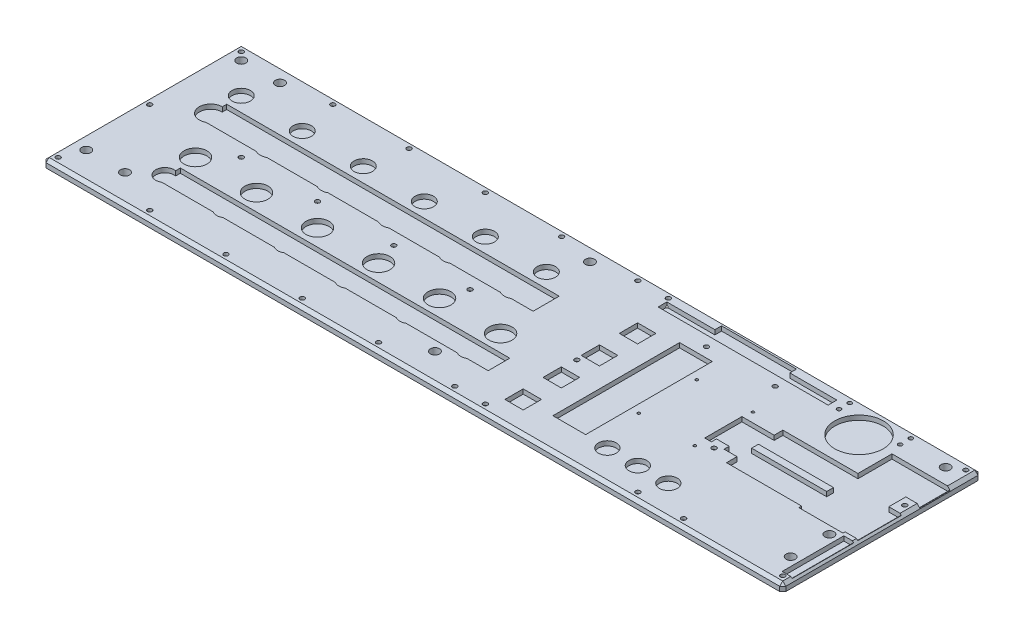
SolidWorks part; units mm, degrees
ref_plane "Front Plane" through (0, 0, 0) normal (0, 0, 1) x (1, 0, 0)
ref_plane "Top Plane" through (0, 0, 0) normal (0, 1, 0) x (1, 0, 0)
ref_plane "Right Plane" through (0, 0, 0) normal (1, 0, 0) x (0, 0, -1)
sketch "Sketch1" plane through (0, 0, 0) normal (0, 1, 0) x (1, 0, 0)
  line L1 (-180, 70) -> (305, 70)
  line L2 (-180, 70) -> (-180, -60)
  line L3 (-180, -60) -> (305, -60)
  line L4 (305, 70) -> (305, -60)
extrude "Boss-Extrude1" add sketch "Sketch1" against normal blind 5 from offset 1.6 offset against normal yes
sketch "Sketch2" plane through (0, -1.6, 0) normal (0, 1, 0) x (1, 0, 0)
  line L0 (305, 70) -> (-180, 70) construction
  line L1 (305, -60) -> (305, 70) construction
  line L2 (-180, 70) -> (-180, -60) construction
  circle A0 centre (245, 50.5) radius 15.0148 construction
  circle A1 centre (291.8, 60) radius 3
  circle A2 centre (-170, 60) radius 3
  circle A3 centre (-144.6, 60) radius 3
  circle A4 centre (58.6, 60) radius 3
  circle A5 centre (291.8, -16.2) radius 3
  circle A6 centre (291.8, -41.6) radius 3
  circle A7 centre (300, -55) radius 1.5
  circle A8 centre (-170, -41.6) radius 3
  circle A9 centre (-144.6, -41.6) radius 3
  circle A10 centre (58.6, -41.6) radius 3
  circle A11 centre (-175, 65) radius 1.5
  circle A12 centre (-115, 65) radius 1.5
  circle A13 centre (-65, 65) radius 1.5
  circle A14 centre (-15, 65) radius 1.5
  circle A15 centre (35, 65) radius 1.5
  circle A16 centre (85, 65) radius 1.5
  circle A17 centre (105, 65) radius 1.5
  circle A18 centre (300, 65) radius 1.5
  circle A19 centre (85, -55) radius 1.5
  circle A20 centre (105, -55) radius 1.5
  circle A21 centre (205, -55) radius 1.5
  circle A22 centre (235, -55) radius 1.5
  circle A23 centre (-175, -55) radius 1.5
  circle A24 centre (-115, -55) radius 1.5
  circle A25 centre (-65, -55) radius 1.5
  circle A26 centre (-15, -55) radius 1.5
  circle A27 centre (35, -55) radius 1.5
  circle A28 centre (-175, 5) radius 1.5
  circle A29 centre (-115, 5) radius 1.5
  circle A30 centre (-65, 5) radius 1.5
  circle A31 centre (110, 0) radius 1.5
  circle A32 centre (35, 5) radius 1.5
  circle A33 centre (-15, 5) radius 1.5
  circle A34 centre (205, -5) radius 1.5
  circle A35 centre (145, 50) radius 1.5
  circle A36 centre (190, 50) radius 1.5
  circle A37 centre (300, 25) radius 1.5
  circle A38 centre (160.54, 28.1) radius 0.879
  circle A39 centre (197.37, 28.1) radius 0.879
  circle A40 centre (197.37, -10) radius 0.879
  circle A41 centre (160.54, -10) radius 0.879
  dimension "D3" = 3
  dimension "D1" = 19.5
  dimension "D2" = 60
  dimension "D4" = 20
  dimension "D5" = 265
extrude "Cut-Extrude1" cut sketch "Sketch2" against normal through all
sketch "Sketch3" plane through (0, -1.6, 0) normal (0, 1, 0) x (1, 0, 0)
  line L0 (305, 70) -> (-180, 70) construction
  line L1 (305, -60) -> (305, 70) construction
  line L2 (208.9224, -2.3883) -> (217.3882, -2.3883)
  line L3 (266.5908, 50) -> (303.9819, 50)
  line L4 (266.5908, 50) -> (266.5908, 30.0739)
  line L5 (266.5908, 30.0739) -> (303.9819, 30.0739)
  line L6 (303.9819, 50) -> (303.9819, 30.0739)
  line L7 (288.3592, 18.9249) -> (303.1307, 18.9249)
  line L8 (288.3592, 18.9249) -> (288.3592, -9.6619)
  line L9 (288.3592, -9.6619) -> (303.1307, -9.6619)
  line L10 (303.1307, 18.9249) -> (303.1307, -9.6619)
  line L11 (297.3726, -12.3054) -> (303.1307, -12.3054)
  line L12 (297.3726, -12.3054) -> (297.3726, -52.7789)
  line L13 (297.3726, -52.7789) -> (303.1307, -52.7789)
  line L14 (303.1307, -12.3054) -> (303.1307, -52.7789)
  line L15 (217.3882, 27.6953) -> (268.8536, 27.6953)
  line L16 (217.3882, 27.6953) -> (217.3882, 21.977)
  line L17 (217.3882, 11.7004) -> (268.8536, 11.7004)
  line L18 (268.8536, 27.6953) -> (268.8536, 11.7004)
  line L19 (268.8536, 7.2252) -> (217.3882, 7.2252)
  line L20 (268.8536, 7.2252) -> (268.8536, -9.267)
  line L21 (268.8536, -9.267) -> (217.3882, -9.267)
  line L22 (217.3882, -2.3883) -> (217.3882, -9.267)
  line L23 (196.255, 21.977) -> (217.3882, 21.977)
  line L24 (196.255, 21.977) -> (196.255, -2.3883)
  line L25 (196.255, -2.3883) -> (200.5925, -2.3883)
  line L26 (217.3882, 11.7004) -> (217.3882, 7.2252)
  line L27 (108.8347, 41) -> (120.8347, 41)
  line L28 (108.8347, 41) -> (108.8347, 29)
  line L29 (108.8347, 29) -> (120.8347, 29)
  line L30 (120.8347, 41) -> (120.8347, 29)
  line L35 (133.8233, 43.5526) -> (139.6368, 43.5526)
  line L36 (133.8233, 43.5526) -> (133.8233, -39.498)
  line L37 (133.8233, -39.498) -> (139.6368, -39.498)
  line L39 (149.7413, 43.5526) -> (155.278, 43.5526)
  line L41 (149.7413, -39.498) -> (155.278, -39.498)
  line L42 (155.278, 43.5526) -> (155.278, -39.498)
  line L43 (106.5809, 62.4515) -> (138.0479, 62.4515)
  line L44 (106.5809, 62.4515) -> (106.5809, 56.7168)
  line L45 (106.5809, 56.7168) -> (218.015, 56.7168)
  line L46 (218.015, 62.4515) -> (218.015, 56.7168)
  line L47 (108.8347, 16) -> (120.8347, 16)
  line L48 (108.8347, 16) -> (108.8347, 4)
  line L49 (108.8347, 4) -> (120.8347, 4)
  line L50 (120.8347, 16) -> (120.8347, 4)
  line L51 (108.8347, -9) -> (120.8347, -9)
  line L52 (108.8347, -9) -> (108.8347, -21)
  line L53 (108.8347, -21) -> (120.8347, -21)
  line L54 (120.8347, -9) -> (120.8347, -21)
  line L55 (108.8347, -34) -> (120.8347, -34)
  line L56 (108.8347, -34) -> (108.8347, -46)
  line L57 (108.8347, -46) -> (120.8347, -46)
  line L58 (120.8347, -34) -> (120.8347, -46)
  line L60 (200.5925, -2.3883) -> (200.5925, 0.933)
  line L61 (200.5925, 0.933) -> (208.9224, 0.933)
  line L62 (208.9224, -2.3883) -> (208.9224, 0.933)
  line L63 (187.1845, 62.4515) -> (218.015, 62.4515)
  line L65 (138.0479, 62.4515) -> (138.0479, 66.8297)
  line L66 (138.0479, 66.8297) -> (187.1845, 66.8297)
  line L67 (187.1845, 62.4515) -> (187.1845, 66.8297)
  line L69 (139.6368, 43.5526) -> (149.7413, 43.5526)
  line L71 (139.6368, -39.498) -> (149.7413, -39.498)
  circle A0 centre (245, 50) radius 15.9002
  circle A1 centre (223.9, 65) radius 1.3177
  circle A2 centre (223.9, 58) radius 1.3177
  circle A3 centre (264, 65) radius 1.3177
  circle A4 centre (264, 58) radius 1.3177
  circle A5 centre (170, -40) radius 5.8588
  circle A6 centre (190, -40) radius 5.8588
  circle A7 centre (210, -40) radius 5.8588
  circle A8 centre (-150, 40) radius 6.0322
  circle A9 centre (-110, 40) radius 6.0322
  circle A10 centre (-70, 40) radius 6.0322
  circle A11 centre (-30, 40) radius 6.0322
  circle A12 centre (10, 40) radius 6.0322
  circle A13 centre (50, 40) radius 6.0322
  circle A14 centre (-130, -30) radius 6.0322
  circle A15 centre (-90, -30) radius 6.0322
  circle A16 centre (-50, -30) radius 6.0322
  circle A17 centre (-10, -30) radius 6.0322
  circle A18 centre (30, -30) radius 6.0322
  circle A19 centre (70, -30) radius 6.0322
  circle A20 centre (-150, 20) radius 7.5246
  circle A21 centre (-70, 20) radius 7.5246
  circle A22 centre (-110, 20) radius 7.5246
  circle A23 centre (-30, 20) radius 7.5246
  circle A24 centre (10, 20) radius 7.5246
  circle A25 centre (50, 20) radius 7.5246
  circle A26 centre (30, -10) radius 7.5246
  circle A27 centre (70, -10) radius 7.5246
  circle A28 centre (-50, -10) radius 7.5246
  circle A29 centre (-10, -10) radius 7.5246
  circle A30 centre (-130, -10) radius 7.5246
  circle A31 centre (-90, -10) radius 7.5246
  dimension "D1" = 20
  dimension "D2" = 60
  dimension "D3" = 12
  dimension "D4" = 25
  dimension "D5" = 25
  dimension "D6" = 25
  dimension "D7" = 29
extrude "Cut-Extrude2" cut sketch "Sketch3" against normal blind 3
chamfer "Chamfer1" distance 2 angle 45 8 edges at (-180, -4.1, -70) (305, -4.1, -70) (305, -4.1, 60) (-180, -4.1, 60) (-180, -1.6, -5) (62.5, -1.6, 60) (62.5, -1.6, -70) (305, -1.6, -5)
chamfer "Chamfer2" distance 1 angle 79 3 edges at (303.1307, -1.7307, -4.6315) (303.9819, -2.5819, -40.037) (303.1307, -1.7307, 32.5421) first distance on face at (303.4054, -2.0054, -4.2816)
sketch "Sketch4" plane through (0, -6.6, 0) normal (0, -1, 0) x (1, 0, 0)
  circle A0 centre (-175, 55) radius 3.5
  circle A1 centre (-115, 55) radius 3.5
  circle A2 centre (-175, -5) radius 3.5
  circle A3 centre (-115, -5) radius 3.5
  circle A4 centre (-115, -65) radius 3.5
  circle A5 centre (-175, -65) radius 3.5
  circle A6 centre (-65, 55) radius 3.5
  circle A7 centre (-15, 55) radius 3.5
  circle A8 centre (35, 55) radius 3.5
  circle A9 centre (85, 55) radius 3.5
  circle A10 centre (105, 55) radius 3.5
  circle A11 centre (-65, -5) radius 3.5
  circle A12 centre (-15, -5) radius 3.5
  circle A13 centre (35, -5) radius 3.5
  circle A14 centre (35, -65) radius 3.5
  circle A15 centre (-15, -65) radius 3.5
  circle A16 centre (-65, -65) radius 3.5
  circle A17 centre (85, -65) radius 3.5
  circle A18 centre (105, -65) radius 3.5
  circle A19 centre (110, 0) radius 3.5
  circle A20 centre (145, -50) radius 3.5
  circle A21 centre (190, -50) radius 3.5
  circle A22 centre (300, -65) radius 3.5
  circle A23 centre (300, 55) radius 3.5
  circle A24 centre (300, -25) radius 3.5
  circle A25 centre (205, 5) radius 3.5
  circle A26 centre (205, 55) radius 3.5
  circle A27 centre (235, 55) radius 3.5
  circle A28 centre (197.37, 10) radius 3.5
  circle A29 centre (160.54, 10) radius 3.5
  circle A30 centre (160.54, -28.1) radius 3.5
  circle A31 centre (197.37, -28.1) radius 3.5
  dimension "D1" = 7
extrude "Cut-Extrude3" cut sketch "Sketch4" against normal blind 3
sketch "Sketch5" plane through (0, -1.6, 0) normal (0, 1, 0) x (1, 0, 0)
  line L1 (-149.9612, 30.4267) -> (68.006, 30.4267)
  line L2 (-149.9612, 30.4267) -> (-149.9612, 13.3473)
  line L3 (-149.9612, 13.3473) -> (68.006, 13.3473)
  line L4 (68.006, 30.4267) -> (68.006, 13.3473)
  line L5 (-128.9322, -20.9775) -> (87.0323, -20.9775)
  line L6 (-128.9322, -20.9775) -> (-128.9322, -35.1528)
  line L7 (-128.9322, -35.1528) -> (87.0323, -35.1528)
  line L8 (87.0323, -20.9775) -> (87.0323, -35.1528)
  line L9 (266.5908, 30.0739) -> (295.5961, 30.0739)
  line L10 (266.5908, 30.0739) -> (266.5908, -11.071)
  line L11 (266.5908, -11.071) -> (295.5961, -11.071)
  line L12 (295.5961, 30.0739) -> (295.5961, -11.071)
extrude "Cut-Extrude5" cut sketch "Sketch5" against normal blind 3
